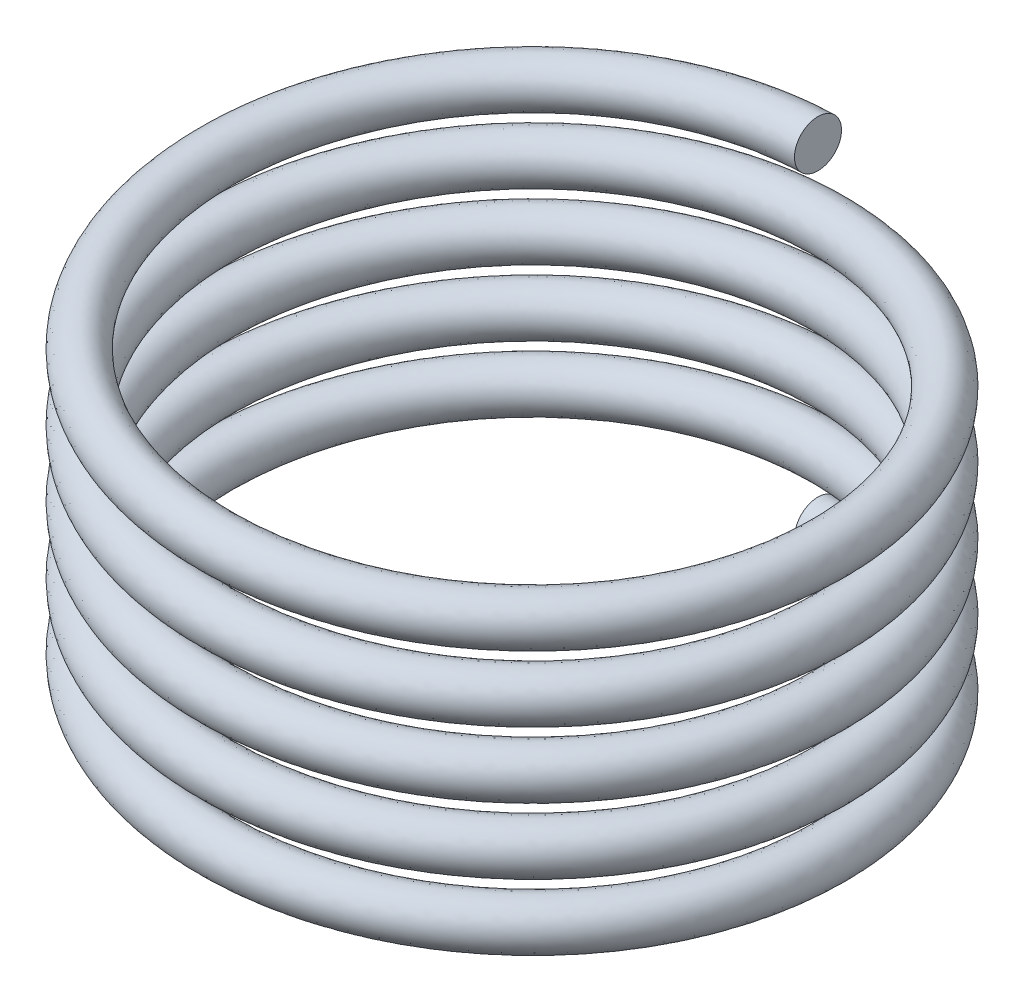
SolidWorks part; units mm, degrees
note: '?' marks a value the reader was unsure of.
ref_plane "Front Plane" through (0, 0, 0) normal (0, 0, 1) x (1, 0, 0)
ref_plane "Top Plane" through (0, 0, 0) normal (0, 1, 0) x (1, 0, 0)
ref_plane "Right Plane" through (0, 0, 0) normal (1, 0, 0) x (0, 0, -1)
sketch "Sketch1" plane through (0, 0, 0) normal (0, 1, 0) x (1, 0, 0)
  circle A0 centre (0, 0) radius 8.255
curve "Helix/Spiral1" pitch 1.778 height 8.89 turns 5
sketch "Sketch2" plane through (0, 0, 0) normal (1, 0, 0) x (0, 0, -1)
  circle A0 centre (8.255, 0) radius 0.635
  spline S0 degree 3 poles (8.255, 0) (8.255, 0.0368) (7.8252, 0.1112) (5.9891, 0.2222) (3.2413, 0.3334) (0, 0.4445) (-3.2413, 0.5556) (-5.9891, 0.6667) (-7.8252, 0.7779) (-8.4699, 0.889) (-7.8252, 1.0001) (-5.9891, 1.1112) (-2.3253, 1.2594) (2.3253, 1.4076) (5.9891, 1.5557) (7.8252, 1.6669) (8.4699, 1.778) (7.8252, 1.8891) (5.9891, 2.0002) (2.3253, 2.1484) (-2.3253, 2.2966) (-5.9891, 2.4448) (-7.8252, 2.5559) (-8.4699, 2.667) (-7.8252, 2.7781) (-5.9891, 2.8893) (-2.3253, 3.0374) (2.3253, 3.1856) (5.9891, 3.3338) (7.8252, 3.4449) (8.4699, 3.556) (7.8252, 3.6671) (5.9891, 3.7783) (2.3253, 3.9264) (-2.3253, 4.0746) (-5.9891, 4.2228) (-7.8252, 4.3339) (-8.4699, 4.445) (-7.8252, 4.5561) (-5.9891, 4.6673) (-2.3253, 4.8154) (2.3253, 4.9636) (5.9891, 5.1118) (7.8252, 5.2229) (8.4699, 5.334) (7.8252, 5.4451) (5.9891, 5.5563) (2.3253, 5.7044) (-2.3253, 5.8526) (-5.9891, 6.0008) (-7.8252, 6.1119) (-8.4699, 6.223) (-7.8252, 6.3341) (-5.9891, 6.4453) (-2.3253, 6.5934) (2.3253, 6.7416) (5.9891, 6.8898) (7.8252, 7.0009) (8.4699, 7.112) (7.8252, 7.2231) (5.9891, 7.3343) (2.3253, 7.4824) (-2.3253, 7.6306) (-5.9891, 7.7788) (-7.8252, 7.8899) (-8.4699, 8.001) (-7.8252, 8.1121) (-5.9891, 8.2233) (-3.2413, 8.3344) (0, 8.4455) (3.2413, 8.5566) (5.9891, 8.6678) (7.8252, 8.7788) (8.255, 8.8532) (8.255, 8.89) knots 0 0 0 0 0.0125 0.025 0.0375 0.05 0.0625 0.075 0.0875 0.1 0.1125 0.125 0.1375 0.1625 0.175 0.1875 0.2 0.2125 0.225 0.2375 0.2625 0.275 0.2875 0.3 0.3125 0.325 0.3375 0.3625 0.375 0.3875 0.4 0.4125 0.425 0.4375 0.4625 0.475 0.4875 0.5 0.5125 0.525 0.5375 0.5625 0.575 0.5875 0.6 0.6125 0.625 0.6375 0.6625 0.675 0.6875 0.7 0.7125 0.725 0.7375 0.7625 0.775 0.7875 0.8 0.8125 0.825 0.8375 0.8625 0.875 0.8875 0.9 0.9125 0.925 0.9375 0.95 0.9625 0.975 0.9875 1 1 1 1 construction
sweep "Peregrine Spring" add profiles "Sketch2" path "Helix/Spiral1"
ref_axis "Axis1" through (0, -2.9337, 0) along (0, 1, 0)?
